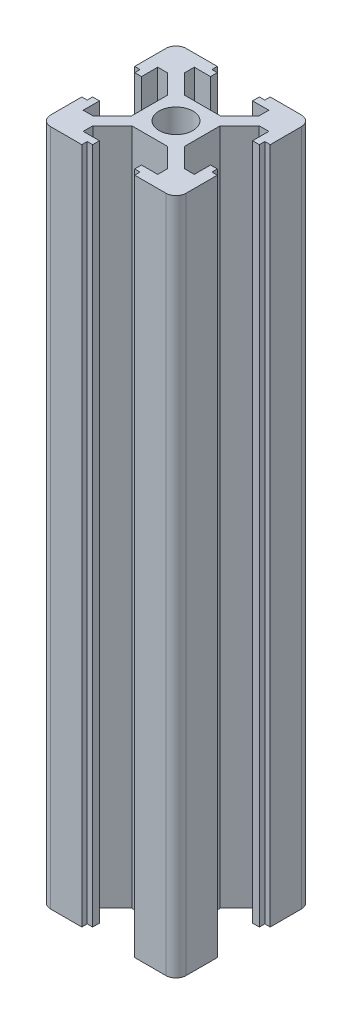
SolidWorks part; units mm, degrees
material "6063-O"
ref_plane "Front Plane" through (0, 0, 0) normal (0, 0, 1) x (1, 0, 0)
ref_plane "Top Plane" through (0, 0, 0) normal (0, 1, 0) x (1, 0, 0)
ref_plane "Right Plane" through (0, 0, 0) normal (1, 0, 0) x (0, 0, -1)
sketch "Sketch1" plane through (0, 0, 0) normal (0, 1, 0) x (1, 0, 0)
  line L0 (0, 14.5399) -> (0, 10) construction
  line L1 (-16.8658, 0) -> (2.5, 0) construction
  line L2 (13.2784, 3.9) -> (3.9, 3.9) construction
  line L3 (0, 0) -> (2.5, 0)
  line L4 (0, 0) -> (0, 2.5)
  line L5 (3.9, 10) -> (8.5, 10)
  line L6 (9.2, 0) -> (16.4291, 0) construction
  line L7 (-2.63, 3.9) -> (2.63, 3.9)
  line L9 (2.5491, 3.9) -> (2.63, 3.9)
  line L10 (3.9, 0) -> (3.9, 2.63)
  line L11 (13.2784, 3.1) -> (2.5491, 3.1) construction
  line L12 (8.2, 7.5573) -> (8.2, -3.0868) construction
  line L13 (9.2, 7.2593) -> (9.2, -8.1534) construction
  line L14 (10, 3.9) -> (9.2, 3.9)
  line L15 (9.2, 3.9) -> (9.2, 3.1)
  line L16 (9.2, 3.1) -> (8.2, 3.1)
  line L17 (8.2, 3.1) -> (8.2, 5.5)
  line L18 (8.2, 5.5) -> (6.77, 5.5)
  line L19 (6.77, 5.5) -> (3.9, 2.63)
  line L20 (5.0973, 5.5) -> (13.0082, 5.5) construction
  line L21 (3.1, 11.2046) -> (3.1, 2.6994) construction
  line L22 (3.9, 10.7498) -> (3.9, 3.9) construction
  line L23 (5.5, 11.523) -> (5.5, 1.4941) construction
  line L24 (-2.2597, 8.2) -> (6.1545, 8.2) construction
  line L25 (-2.9419, 9.2) -> (5.7225, 9.2) construction
  line L26 (3.9, 10) -> (3.9, 9.2)
  line L27 (3.9, 9.2) -> (3.1, 9.2)
  line L28 (3.1, 9.2) -> (3.1, 8.2)
  line L29 (3.1, 8.2) -> (5.5, 8.2)
  line L30 (5.5, 8.2) -> (5.5, 6.77)
  line L31 (5.5, 6.77) -> (2.63, 3.9)
  line L32 (0, 2.5) -> (0, -14.4122) construction
  line L33 (10, 3.9) -> (10, 8.5)
  line L34 (9.2, 0) -> (10, 0)
  line L35 (2.63, 3.9) -> (2.5491, 3.9) construction
  line L36 (3.9, 2.63) -> (3.9, 2.0627) construction
  line L37 (10, -3.9) -> (10, -8.5)
  line L38 (3.9, -10) -> (8.5, -10)
  line L39 (3.9, -10) -> (3.9, -9.2)
  line L40 (3.9, -9.2) -> (3.1, -9.2)
  line L41 (3.1, -9.2) -> (3.1, -8.2)
  line L42 (3.1, -8.2) -> (5.5, -8.2)
  line L43 (5.5, -8.2) -> (5.5, -6.77)
  line L44 (5.5, -6.77) -> (2.63, -3.9)
  line L45 (0, -3.9) -> (2.63, -3.9)
  line L46 (3.9, 0) -> (3.9, -2.63)
  line L47 (6.77, -5.5) -> (3.9, -2.63)
  line L48 (8.2, -5.5) -> (6.77, -5.5)
  line L49 (8.2, -3.1) -> (8.2, -5.5)
  line L50 (9.2, -3.1) -> (8.2, -3.1)
  line L51 (9.2, -3.9) -> (9.2, -3.1)
  line L52 (10, -3.9) -> (9.2, -3.9)
  line L53 (-3.9, -10) -> (-8.5, -10)
  line L54 (-10, -3.9) -> (-10, -8.5)
  line L55 (-10, -3.9) -> (-9.2, -3.9)
  line L56 (-9.2, -3.9) -> (-9.2, -3.1)
  line L57 (-9.2, -3.1) -> (-8.2, -3.1)
  line L58 (-8.2, -3.1) -> (-8.2, -5.5)
  line L59 (-8.2, -5.5) -> (-6.77, -5.5)
  line L60 (-6.77, -5.5) -> (-3.9, -2.63)
  line L61 (-3.9, 0) -> (-3.9, -2.63)
  line L62 (0, -3.9) -> (-2.63, -3.9)
  line L63 (-5.5, -6.77) -> (-2.63, -3.9)
  line L64 (-5.5, -8.2) -> (-5.5, -6.77)
  line L65 (-3.1, -8.2) -> (-5.5, -8.2)
  line L66 (-3.1, -9.2) -> (-3.1, -8.2)
  line L67 (-3.9, -9.2) -> (-3.1, -9.2)
  line L68 (-3.9, -10) -> (-3.9, -9.2)
  line L69 (-10, 3.9) -> (-10, 8.5)
  line L70 (-3.9, 10) -> (-8.5, 10)
  line L71 (-3.9, 10) -> (-3.9, 9.2)
  line L72 (-3.9, 9.2) -> (-3.1, 9.2)
  line L73 (-3.1, 9.2) -> (-3.1, 8.2)
  line L74 (-3.1, 8.2) -> (-5.5, 8.2)
  line L75 (-5.5, 8.2) -> (-5.5, 6.77)
  line L76 (-5.5, 6.77) -> (-2.63, 3.9)
  line L78 (-3.9, 0) -> (-3.9, 2.63)
  line L79 (-6.77, 5.5) -> (-3.9, 2.63)
  line L80 (-8.2, 5.5) -> (-6.77, 5.5)
  line L81 (-8.2, 3.1) -> (-8.2, 5.5)
  line L82 (-9.2, 3.1) -> (-8.2, 3.1)
  line L83 (-9.2, 3.9) -> (-9.2, 3.1)
  line L84 (-10, 3.9) -> (-9.2, 3.9)
  line L85 (0, 3.9) -> (-2.63, 3.9) [skipped]
  circle A0 centre (0, 0) radius 2.5
  arc A1 (8.5, 10) -> (10, 8.5) centre (8.5, 8.5) cw
  arc A2 (10, -8.5) -> (8.5, -10) centre (8.5, -8.5) cw
  arc A4 (-8.5, -10) -> (-10, -8.5) centre (-8.5, -8.5) cw
  arc A6 (-10, 8.5) -> (-8.5, 10) centre (-8.5, 8.5) cw
  point P12 (10, 10)
  point P126 (0, 0)
  dimension "D3" = 5
  dimension "D4" = 1.5
  dimension "D1" = 10
  dimension "D2" = 10
  dimension "D6" = 3.9
  dimension "D7" = 3.9
  dimension "D8" = 3.1
  dimension "D9" = 4
  dimension "D11" = 5.5
  dimension "D12" = 1.8
  dimension "D13" = 0.8
  dimension "D14" = 3.9
  dimension "D15" = 3.1
  dimension "D16" = 5.5
  dimension "D17" = 1.27
  dimension "D18" = 1.27
  dimension "D19" = 1.27
  dimension "D20" = 1.27
extrude "Boss-Extrude1" add sketch "Sketch1" along normal blind 100 contours A6 L69 L84 L83 L82 L81 L80 L79 L78 L61 L60 L59 L58 L57 L56 L55 L54 A4 L53 L68 L67 L66 L65 L64 L63 L62 L45 L44 L43 L42 L41 L40 L39 L38 A2 L37 L52 L51 L50 L49 L48 L47 L46 L10 L19 L18 L17 L16 L15 L14 L33 region at (6.2, 0, -9.7172)
